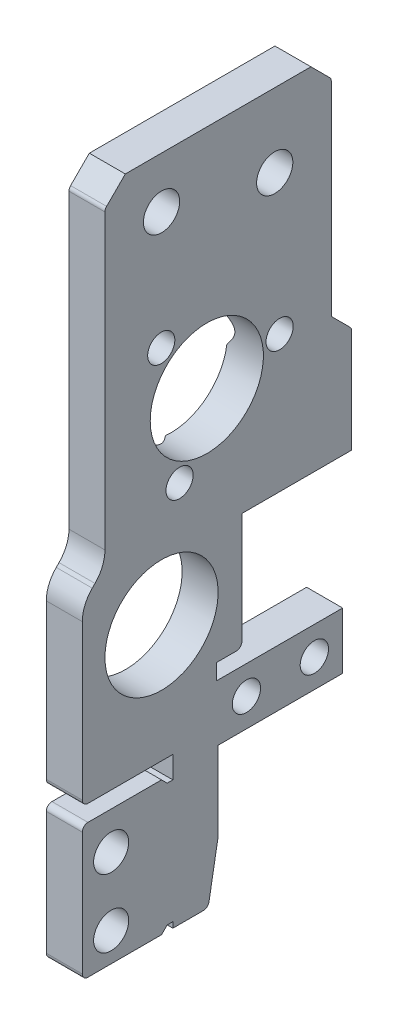
SolidWorks part; units mm, degrees
ref_plane "Front Plane" through (0, 0, 0) normal (0, 0, 1) x (1, 0, 0)
ref_plane "Top Plane" through (0, 0, 0) normal (0, 1, 0) x (1, 0, 0)
ref_plane "Right Plane" through (0, 0, 0) normal (1, 0, 0) x (0, 0, -1)
sketch "Sketch1" plane through (0, 0, 0) normal (1, 0, 0) x (0, 0, -1)
  line L2 (0, 0) -> (0, 11.85)
  line L3 (0, 28.7) -> (2, 30.7)
  line L4 (2, 30.7) -> (2, 59.81)
  line L5 (2, 59.81) -> (22, 59.81)
  line L7 (23.8, 28.68) -> (14.1, 28.68)
  line L8 (11.85, 18.4) -> (11.85, 17)
  line L9 (11.85, 17) -> (23, 17)
  line L10 (23, 17) -> (23, 12)
  line L11 (23, 12) -> (12, 12)
  line L12 (12, 12) -> (12, 0)
  line L13 (12, 0) -> (8, 0)
  line L14 (-8.9356, -4) -> (60.4069, -4) construction
  line L15 (7, 28.7) -> (0, 28.7) construction
  line L16 (2, 30.7) -> (2, 20.9492) construction
  line L17 (0, 11.85) -> (7, 11.85)
  line L18 (11.85, 18.4) -> (14.1, 18.4)
  line L19 (14.1, 18.4) -> (14.1, 28.68)
  line L23 (22, 59.81) -> (22, 39.81)
  line L26 (22, 39.81) -> (23.8, 39.81)
  line L27 (23.8, 39.81) -> (23.8, 28.68)
  line L30 (8, 11.35) -> (8, 13.3)
  line L31 (8, 13.3) -> (0, 13.3)
  line L32 (0, 13.3) -> (0, 28.7)
  line L33 (7, 11.85) -> (7.5, 11.35)
  line L34 (7.5, 11.35) -> (8, 11.35)
  line L35 (8, 0) -> (8, 0.5)
  line L36 (8, 0.5) -> (7.5, 0.5)
  line L37 (7.5, 0.5) -> (7, 0)
  line L38 (7, 0) -> (0, 0)
  circle A0 centre (7, 23.7) radius 5
  circle A1 centre (7, 55.31) radius 1.6
  circle A2 centre (17, 53.31) radius 1.6
  circle A3 centre (20.5, 14.5) radius 1.25
  circle A4 centre (14.5, 14.5) radius 1.25
  circle A5 centre (2.55, 2.55) radius 1.55
  circle A6 centre (2.55, 8.55) radius 1.55
  point P12 (0, 0)
  point P46 (0, 0)
  dimension "D11" = 10
  dimension "D13" = 3.2
  dimension "D17" = 5
  dimension "D21" = 2.5
  dimension "D29" = 6
  dimension "D28" = 3.1
  dimension "D30" = 2.55
  dimension "D3" = 31.13
  dimension "D4" = 5
  dimension "D5" = 11.68
  dimension "D6" = 11.15
  dimension "D7" = 10
  dimension "D8" = 4
  dimension "D9" = 2
  dimension "D10" = 2
  dimension "D12" = 36.11
  dimension "D14" = 6.5
  dimension "D15" = 4.5
  dimension "D16" = 5
  dimension "D18" = 6
  dimension "D19" = 2.5
  dimension "D20" = 2.5
  dimension "D22" = 1.4
  dimension "D23" = 2.25
  dimension "D24" = 20
  dimension "D25" = 11
  dimension "D26" = 1.8
  dimension "D27" = 20
  dimension "D31" = 2.55
  dimension "D32" = 11.85
  dimension "D33" = 7
  dimension "D34" = 0.5
  dimension "D35" = 0.5
  dimension "D36" = 1.45
  dimension "D37" = 0.5
  dimension "D38" = 59.81
extrude "Boss-Extrude1" add sketch "Sketch1" along normal blind 3.18
chamfer "Chamfer1" distance 5 angle 10 1 edges at (1.59, 0, -12) first distance on face at (1.59, 6, -12)
fillet "Fillet1" [suppressed] radius 1
sketch "Sketch3" plane through (0, 0, 0) normal (-1, 0, 0) x (0, 0, 1)
  line L1 (-17.4326, 40.7448) -> (-6.9749, 44.9147) construction
  line L2 (-6.9749, 44.9147) -> (-8.5925, 33.7732) construction
  line L3 (-8.5925, 33.7732) -> (-17.4326, 40.7448) construction
  line L4 (-2, 59.81) -> (-2, 30.7) construction
  circle A0 centre (-11, 39.8109) radius 5
  circle A2 centre (-11, 39.8109) radius 6.5 construction
  circle A3 centre (-6.9749, 44.9147) radius 1.2 construction
  circle A4 centre (-8.5925, 33.7732) radius 1.2 construction
  circle A5 centre (-17.4326, 40.7448) radius 1.2 construction
  circle A6 centre (-7, 23.7) radius 5 construction
  dimension "D1" = 10
  dimension "D3" = 16.6
  dimension "D4" = 13
  dimension "D5" = 2.4
  dimension "D2" = 9
hole_wizard "CSK for M2 Flat Head Machine Screw1" positions "Sketch6" profile "Sketch7" countersink size "M2" standard "ANSI Metric"
sketch "Sketch6" plane through (0, 0, 0) normal (-1, 0, 0) x (0, 0, 1)
  point P0 (-6.9749, 44.9147)
  point P3 (-17.4326, 40.7448)
  point P6 (-8.5925, 33.7732)
sketch "Sketch7" plane through (0, 44.9147, -6.9749) normal (0, 1, 0) x (0, 0, 1)
  line L0 (0, 0) -> (0, 4.23)
  line L1 (0, 4.23) -> (1.2, 3.509)
  line L2 (1.2, 3.509) -> (1.2, 1)
  line L3 (1.2, 1) -> (2.2, 0)
  line L5 (2.2, 0) -> (0, 0)
  line L6 (-1.2, 1) -> (-2.2, 0) construction
  line L10 (0, 4.23) -> (-1.2, 3.509) construction
  line L11 (0, -6.35) -> (0, 107.95) construction
  dimension "Hole Dia." = 2.4
  dimension "Hole Depth" = 4.23
  dimension "Near C'Sink Dia." = 4.4
  dimension "Near C'Sink Angle" = 90
  dimension "Drill Angle" = 118
extrude "Cut-Extrude4" cut sketch "Sketch3" against normal through all
sketch "Sketch8" plane through (3.18, 0, 0) normal (1, 0, 0) x (0, 0, -1)
  line L0 (2, 59.81) -> (2, 30.7) construction
  line L1 (11, 39.8109) -> (2, 39.8109) construction
  line L2 (2, 42.8109) -> (4.1261, 42.8109)
  line L3 (4.1261, 36.8109) -> (2, 36.8109)
  line L4 (2, 36.8109) -> (2, 42.8109)
  arc A0 (4.1261, 36.8109) -> (4.1261, 42.8109) centre (11, 39.8109) ccw
  circle A1 centre (7, 23.7) radius 5 construction
  point P11 (2, 39.8109)
  dimension "D1" = 16.6
  dimension "D2" = 15
  dimension "D3" = 9
  dimension "D4" = 6
extrude "Cut-Extrude5" [suppressed] cut sketch "Sketch8" against normal through all
fillet "Fillet2" radius 3 2 edges at (1.59, 30.7, -2) (1.59, 28.7, 0)
fillet "Chamfer2" radius 1.8 3 edges at (1.59, 59.81, -22) (1.59, 59.81, -2) (1.59, 39.81, -23.8) profile chamfer
fillet "Fillet4" radius 0.5 8 edges at (1.59, 58.01, -2) (1.59, 58.01, -22) (1.59, 18.4, -14.1) (1.59, 0, -11.1184) (1.59, 38.01, -23.8) (1.59, 13.3, 0) (1.59, 11.85, 0) (1.59, 0, 0)
